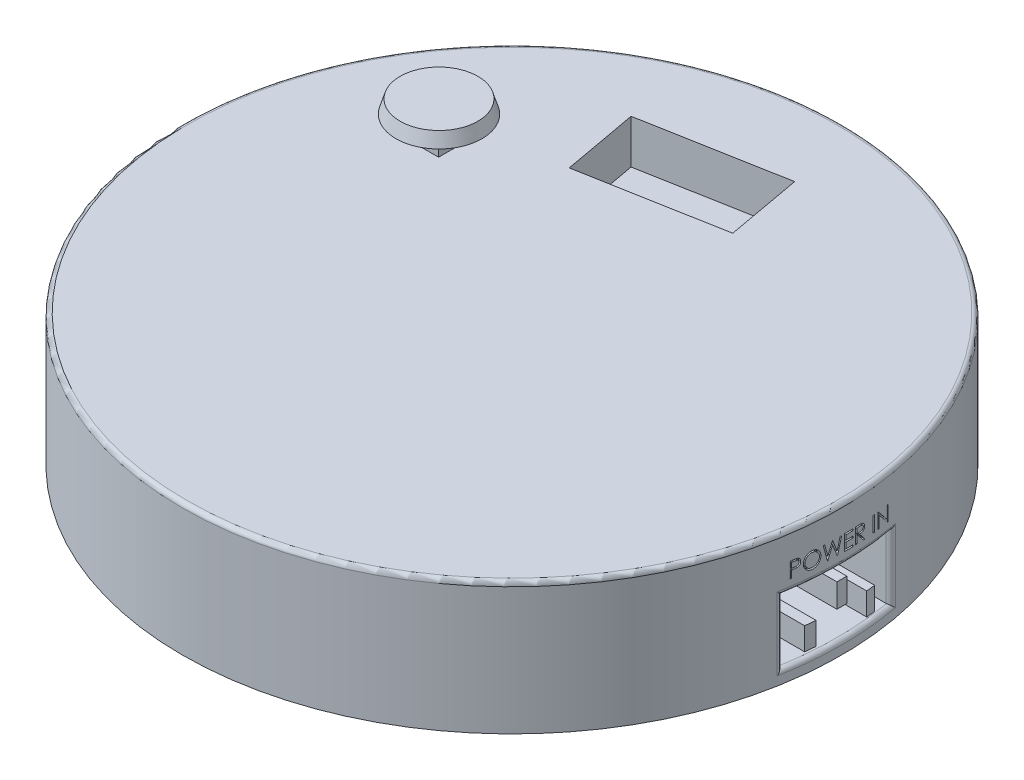
SolidWorks part; units mm, degrees
ref_plane "Front Plane" through (0, 0, 0) normal (0, 0, 1) x (1, 0, 0)
ref_plane "Top Plane" through (0, 0, 0) normal (0, 1, 0) x (1, 0, 0)
ref_plane "Right Plane" through (0, 0, 0) normal (1, 0, 0) x (0, 0, -1)
sketch "Sketch1" plane through (0, 0, 0) normal (0, 1, 0) x (1, 0, 0)
  circle A0 centre (0, 0) radius 75
  dimension "D1" = 150
extrude "Boss-Extrude1" add sketch "Sketch1" along normal blind 30
ref_plane "Plane1" through (75, 0, 0) normal (1, 0, 0) x (0, 0, -1)
sketch "Sketch3" plane through (75, 0, 0) normal (1, 0, 0) x (0, 0, -1)
  line L1 (-12.2687, 2.998) -> (12.2687, 2.998)
  line L2 (-12.2687, 2.998) -> (-12.2687, 17.5782)
  line L3 (-12.2687, 17.5782) -> (12.2687, 17.5782)
  line L4 (12.2687, 2.998) -> (12.2687, 17.5782)
  line L5 (-12.2687, 2.998) -> (12.2687, 17.5782) construction
  line L6 (-12.2687, 17.5782) -> (12.2687, 2.998) construction
  line L7 (-1.057, 14.9744) -> (1.2028, 14.9744)
  line L8 (-1.057, 14.9744) -> (-1.057, 9.5734)
  line L9 (-1.057, 9.5734) -> (1.2028, 9.5734)
  line L10 (1.2028, 14.9744) -> (1.2028, 9.5734)
  line L11 (-7.9765, 9.5734) -> (-5.6137, 9.5734)
  line L12 (-7.9765, 9.5734) -> (-7.9765, 4.4263)
  line L13 (-7.9765, 4.4263) -> (-5.6137, 4.4263)
  line L14 (-5.6137, 9.5734) -> (-5.6137, 4.4263)
  line L15 (5.947, 9.5734) -> (7.9722, 9.5734)
  line L16 (5.947, 9.5734) -> (5.947, 4.4263)
  line L17 (5.947, 4.4263) -> (7.9722, 4.4263)
  line L18 (7.9722, 9.5734) -> (7.9722, 4.4263)
  point P0 (0, 10.2881)
extrude "Cut-Extrude1" cut sketch "Sketch3" against normal blind 20 contours L1 L4 L3 L2 L7 L10 L9 L8 L11 L14 L13 L12 L15 L18 L17 L16 region at (75, 10.2881, 11.9833)
fillet "Fillet2" radius 1 4 edges at (75, 2.998, 0) (73.9897, 10.2881, 12.2687) (73.9897, 10.2881, -12.2687) (75, 17.5782, 0)
sketch "Sketch4" plane through (75, 0, 0) normal (1, 0, 0) x (0, 0, -1)
  text T0 "POWER IN"
extrude "Cut-Extrude2" cut sketch "Sketch4" against normal blind 1
sketch "Sketch5" plane through (0, 30, 0) normal (0, 1, 0) x (1, 0, 0)
  line L1 (-38.9885, 22.2873) -> (-49.9885, 22.2873)
  line L2 (-38.9885, 22.2873) -> (-38.9885, 33.2873)
  line L3 (-38.9885, 33.2873) -> (-49.9885, 33.2873)
  line L4 (-49.9885, 22.2873) -> (-49.9885, 33.2873)
  dimension "D1" = 11
extrude "Boss-Extrude2" add sketch "Sketch5" along normal blind 3
sketch "Sketch6" plane through (0, 33, 0) normal (0, 1, 0) x (1, 0, 0)
  circle A0 centre (-44.4635, 27.8483) radius 9.7711
extrude "Boss-Extrude3" add sketch "Sketch6" along normal blind 3 draft 17
fillet "Fillet5" radius 1 1 edges at (0, 30, 75)
sketch "Sketch10" plane through (0, 30, 0) normal (0, 1, 0) x (1, 0, 0)
  line L0 (-25.1311, 52.3284) -> (6.3498, 58.069)
  line L1 (6.3498, 58.069) -> (9.4892, 40.8529)
  line L2 (9.4892, 40.8529) -> (-21.9917, 35.1123)
  line L3 (-21.9917, 35.1123) -> (-25.1311, 52.3284)
sketch "Sketch11" plane through (0, 30, 0) normal (0, 1, 0) x (1, 0, 0)
  line L0 (-25.1542, 52.2532) -> (6.3266, 57.9938)
  line L1 (6.3266, 57.9938) -> (9.466, 40.7777)
  line L2 (9.466, 40.7777) -> (-22.0149, 35.0371)
  line L3 (-22.0149, 35.0371) -> (-25.1542, 52.2532)
extrude "Cut-Extrude5" cut sketch "Sketch11" against normal blind 10
